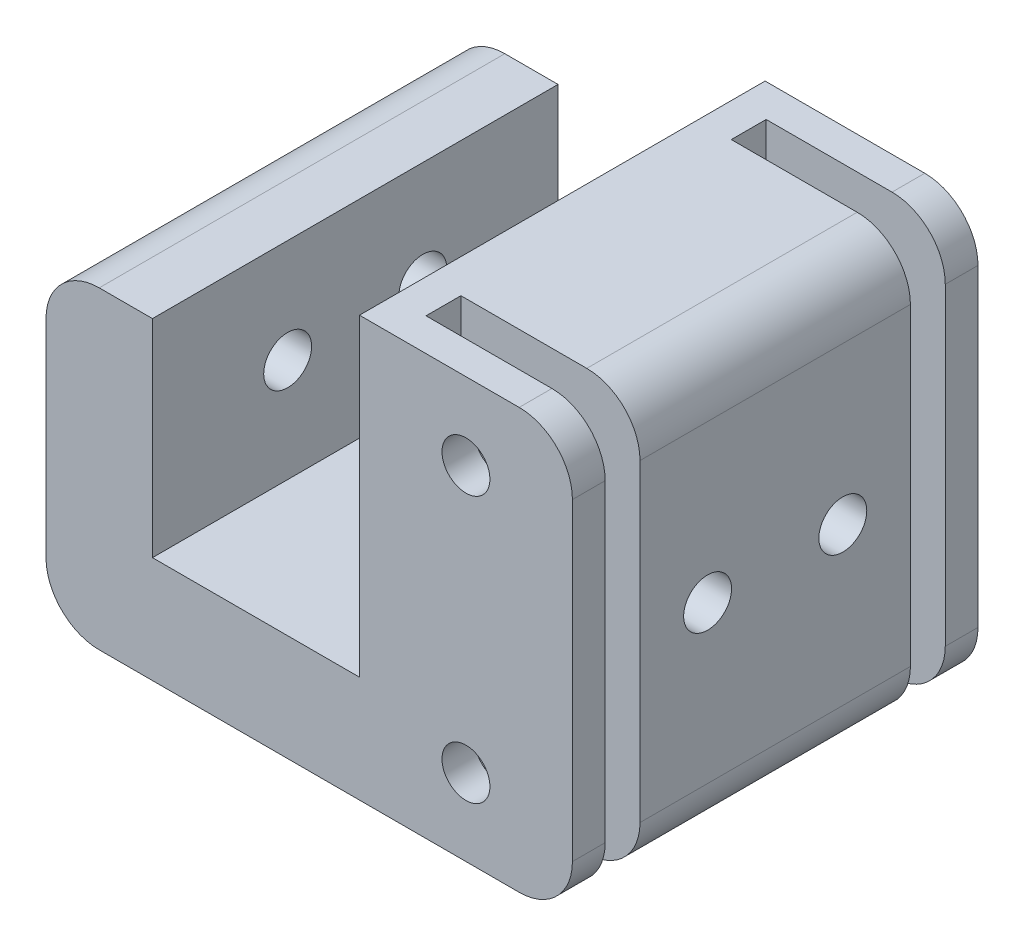
SolidWorks part; units mm, degrees
ref_plane "Front Plane" through (0, 0, 0) normal (0, 0, 1) x (1, 0, 0)
ref_plane "Top Plane" through (0, 0, 0) normal (0, 1, 0) x (1, 0, 0)
ref_plane "Right Plane" through (0, 0, 0) normal (1, 0, 0) x (0, 0, -1)
sketch "Sketch1" plane through (0, 0, 0) normal (0, 0, 1) x (1, 0, 0)
  line L0 (-9.725, 9.725) -> (-14.725, 9.725)
  line L1 (-9.725, -9.725) -> (9.725, -9.725)
  line L2 (-9.725, -9.725) -> (-9.725, 9.725)
  line L3 (-9.725, 9.725) -> (9.725, 9.725) construction
  line L4 (9.725, -9.725) -> (9.725, 9.725)
  line L5 (-9.725, -9.725) -> (9.725, 9.725) construction
  line L6 (-9.725, 9.725) -> (9.725, -9.725) construction
  line L7 (-19.725, 4.725) -> (-19.725, -14.725)
  line L8 (-14.725, -19.725) -> (24.725, -19.725)
  line L9 (29.725, -14.725) -> (29.725, 14.725)
  line L11 (19.725, -12.5) -> (19.725, 12.5) construction
  line L12 (9.725, 9.725) -> (9.725, 19.725)
  line L13 (9.725, 19.725) -> (24.725, 19.725)
  circle A0 centre (19.725, 12.5) radius 2.25
  circle A1 centre (19.725, -12.5) radius 2.25
  arc A3 (24.725, -19.725) -> (29.725, -14.725) centre (24.725, -14.725) ccw
  arc A4 (-19.725, -14.725) -> (-14.725, -19.725) centre (-14.725, -14.725) ccw
  arc A5 (-14.725, 9.725) -> (-19.725, 4.725) centre (-14.725, 4.725) ccw
  arc A6 (24.725, 19.725) -> (29.725, 14.725) centre (24.725, 14.725) cw
  point P0 (0, 0)
  point P8 (29.7233, 16.8521)
  point P11 (19.725, 0)
  point P16 (29.725, 0)
  point P26 (-19.725, 9.725)
  dimension "D5" = 4.5
  dimension "D7" = 10
  dimension "D9" = 5
  dimension "D1" = 19.45
  dimension "D2" = 10
  dimension "D3" = 10
  dimension "D4" = 20
  dimension "D6" = 25
  dimension "D8" = 10
extrude "Boss-Extrude1" add sketch "Sketch1" along normal mid plane 38.1
sketch "Sketch2" plane through (0, 0, 0) normal (0, 1, 0) x (1, 0, 0)
  line L0 (29.725, -19.05) -> (29.725, 19.05) construction
  line L1 (29.725, 15.975) -> (12.9, 15.975)
  line L2 (29.725, 15.975) -> (29.725, 12.7)
  line L3 (29.725, 12.7) -> (12.9, 12.7)
  line L4 (12.9, 15.975) -> (12.9, 12.7)
  line L5 (12.9, -12.7) -> (12.9, 12.7) construction
  line L6 (29.725, -12.7) -> (12.9, -12.7)
  line L7 (29.725, -12.7) -> (29.725, -15.975)
  line L8 (29.725, -15.975) -> (12.9, -15.975)
  line L9 (12.9, -12.7) -> (12.9, -15.975)
  line L12 (9.725, -19.05) -> (9.725, 19.05) construction
  point P10 (12.9, 0)
  dimension "D1" = 3.275
  dimension "D2" = 25.4
  dimension "D3" = 3.175
extrude "Cut-Extrude1" cut sketch "Sketch2" against normal through all both and the other way through all
sketch "Sketch4" plane through (0, 0, 0) normal (1, 0, 0) x (0, 0, -1)
  line L0 (-6.35, 0) -> (6.35, 0) construction
  circle A0 centre (-6.35, 0) radius 2.25
  circle A1 centre (6.35, 0) radius 2.25
  point P4 (0, 0)
  dimension "D1" = 4.5
  dimension "D2" = 12.7
extrude "Cut-Extrude2" cut sketch "Sketch4" against normal through all both and the other way through all
